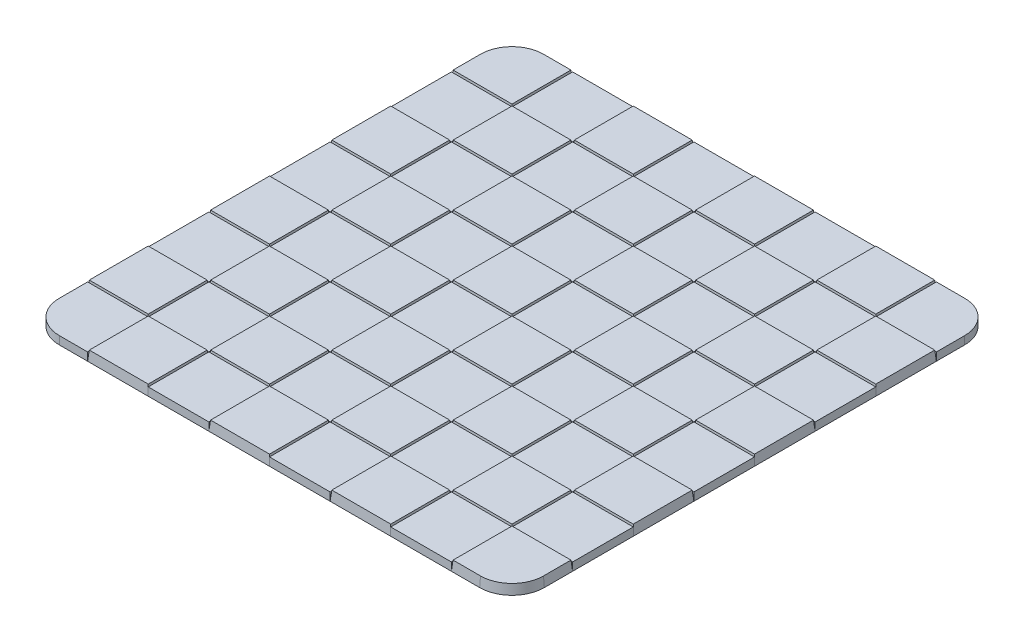
SolidWorks part; units mm, degrees
ref_plane "Front Plane" through (0, 0, 0) normal (0, 0, 1) x (1, 0, 0)
ref_plane "Top Plane" through (0, 0, 0) normal (0, 1, 0) x (1, 0, 0)
ref_plane "Right Plane" through (0, 0, 0) normal (1, 0, 0) x (0, 0, -1)
sketch "Sketch2" plane through (0, 0, 0) normal (0, 1, 0) x (1, 0, 0)
  line L0 (-57.15, 57.15) -> (-38.1, 57.15)
  line L1 (-66.04, 76.2) -> (66.04, 76.2)
  line L2 (-76.2, 66.04) -> (-76.2, -66.04)
  line L3 (-66.04, -76.2) -> (66.04, -76.2)
  line L4 (76.2, 66.04) -> (76.2, -66.04)
  line L5 (-73.2242, 73.2242) -> (73.2242, -73.2242) construction
  line L6 (-73.2242, -73.2242) -> (73.2242, 73.2242) construction
  line L7 (-66.04, 76.2) -> (-57.15, 76.2)
  line L8 (-76.2, 66.04) -> (-76.2, 57.15)
  line L9 (-76.2, 57.15) -> (-57.15, 57.15)
  line L10 (-57.15, 76.2) -> (-57.15, 57.15)
  line L11 (-38.1, 76.2) -> (-38.1, 57.15)
  line L12 (-38.1, 57.15) -> (-19.05, 57.15)
  line L13 (-19.05, 76.2) -> (-19.05, 57.15)
  line L14 (-19.05, 57.15) -> (0, 57.15)
  line L15 (0, 76.2) -> (0, 57.15)
  line L16 (0, 57.15) -> (19.05, 57.15)
  line L17 (19.05, 76.2) -> (19.05, 57.15)
  line L18 (19.05, 57.15) -> (38.1, 57.15)
  line L19 (38.1, 76.2) -> (38.1, 57.15)
  line L20 (38.1, 57.15) -> (57.15, 57.15)
  line L21 (57.15, 76.2) -> (57.15, 57.15)
  line L22 (57.15, 57.15) -> (76.2, 57.15)
  line L23 (76.2, 66.04) -> (76.2, 57.15)
  line L24 (-57.15, 38.1) -> (-38.1, 38.1)
  line L25 (-38.1, 57.15) -> (-38.1, 38.1)
  line L26 (-38.1, 38.1) -> (-19.05, 38.1)
  line L27 (-19.05, 57.15) -> (-19.05, 38.1)
  line L28 (-19.05, 38.1) -> (0, 38.1)
  line L29 (0, 57.15) -> (0, 38.1)
  line L30 (0, 38.1) -> (19.05, 38.1)
  line L31 (19.05, 57.15) -> (19.05, 38.1)
  line L32 (19.05, 38.1) -> (38.1, 38.1)
  line L33 (38.1, 57.15) -> (38.1, 38.1)
  line L34 (38.1, 38.1) -> (57.15, 38.1)
  line L35 (57.15, 57.15) -> (57.15, 38.1)
  line L36 (57.15, 38.1) -> (76.2, 38.1)
  line L37 (76.2, 57.15) -> (76.2, 38.1)
  line L38 (-57.15, 19.05) -> (-38.1, 19.05)
  line L39 (-38.1, 38.1) -> (-38.1, 19.05)
  line L40 (-38.1, 19.05) -> (-19.05, 19.05)
  line L41 (-19.05, 38.1) -> (-19.05, 19.05)
  line L42 (-19.05, 19.05) -> (0, 19.05)
  line L43 (0, 38.1) -> (0, 19.05)
  line L44 (0, 19.05) -> (19.05, 19.05)
  line L45 (19.05, 38.1) -> (19.05, 19.05)
  line L46 (19.05, 19.05) -> (38.1, 19.05)
  line L47 (38.1, 38.1) -> (38.1, 19.05)
  line L48 (38.1, 19.05) -> (57.15, 19.05)
  line L49 (57.15, 38.1) -> (57.15, 19.05)
  line L50 (57.15, 19.05) -> (76.2, 19.05)
  line L51 (76.2, 38.1) -> (76.2, 19.05)
  line L52 (-57.15, 0) -> (-38.1, 0)
  line L53 (-38.1, 19.05) -> (-38.1, 0)
  line L54 (-38.1, 0) -> (-19.05, 0)
  line L55 (-19.05, 19.05) -> (-19.05, 0)
  line L56 (-19.05, 0) -> (0, 0)
  line L57 (0, 19.05) -> (0, 0)
  line L58 (0, 0) -> (19.05, 0)
  line L59 (19.05, 19.05) -> (19.05, 0)
  line L60 (19.05, 0) -> (38.1, 0)
  line L61 (38.1, 19.05) -> (38.1, 0)
  line L62 (38.1, 0) -> (57.15, 0)
  line L63 (57.15, 19.05) -> (57.15, 0)
  line L64 (57.15, 0) -> (76.2, 0)
  line L65 (76.2, 19.05) -> (76.2, 0)
  line L66 (-57.15, -19.05) -> (-38.1, -19.05)
  line L67 (-38.1, 0) -> (-38.1, -19.05)
  line L68 (-38.1, -19.05) -> (-19.05, -19.05)
  line L69 (-19.05, 0) -> (-19.05, -19.05)
  line L70 (-19.05, -19.05) -> (0, -19.05)
  line L71 (0, 0) -> (0, -19.05)
  line L72 (0, -19.05) -> (19.05, -19.05)
  line L73 (19.05, 0) -> (19.05, -19.05)
  line L74 (19.05, -19.05) -> (38.1, -19.05)
  line L75 (38.1, 0) -> (38.1, -19.05)
  line L76 (38.1, -19.05) -> (57.15, -19.05)
  line L77 (57.15, 0) -> (57.15, -19.05)
  line L78 (57.15, -19.05) -> (76.2, -19.05)
  line L79 (76.2, 0) -> (76.2, -19.05)
  line L80 (-57.15, -38.1) -> (-38.1, -38.1)
  line L81 (-38.1, -19.05) -> (-38.1, -38.1)
  line L82 (-38.1, -38.1) -> (-19.05, -38.1)
  line L83 (-19.05, -19.05) -> (-19.05, -38.1)
  line L84 (-19.05, -38.1) -> (0, -38.1)
  line L85 (0, -19.05) -> (0, -38.1)
  line L86 (0, -38.1) -> (19.05, -38.1)
  line L87 (19.05, -19.05) -> (19.05, -38.1)
  line L88 (19.05, -38.1) -> (38.1, -38.1)
  line L89 (38.1, -19.05) -> (38.1, -38.1)
  line L90 (38.1, -38.1) -> (57.15, -38.1)
  line L91 (57.15, -19.05) -> (57.15, -38.1)
  line L92 (57.15, -38.1) -> (76.2, -38.1)
  line L93 (76.2, -19.05) -> (76.2, -38.1)
  line L94 (-57.15, -57.15) -> (-38.1, -57.15)
  line L95 (-38.1, -38.1) -> (-38.1, -57.15)
  line L96 (-38.1, -57.15) -> (-19.05, -57.15)
  line L97 (-19.05, -38.1) -> (-19.05, -57.15)
  line L98 (-19.05, -57.15) -> (0, -57.15)
  line L99 (0, -38.1) -> (0, -57.15)
  line L100 (0, -57.15) -> (19.05, -57.15)
  line L101 (19.05, -38.1) -> (19.05, -57.15)
  line L102 (19.05, -57.15) -> (38.1, -57.15)
  line L103 (38.1, -38.1) -> (38.1, -57.15)
  line L104 (38.1, -57.15) -> (57.15, -57.15)
  line L105 (57.15, -38.1) -> (57.15, -57.15)
  line L106 (57.15, -57.15) -> (76.2, -57.15)
  line L107 (76.2, -38.1) -> (76.2, -57.15)
  line L108 (-57.15, -76.2) -> (-38.1, -76.2)
  line L109 (-38.1, -57.15) -> (-38.1, -76.2)
  line L110 (-38.1, -76.2) -> (-19.05, -76.2)
  line L111 (-19.05, -57.15) -> (-19.05, -76.2)
  line L112 (-19.05, -76.2) -> (0, -76.2)
  line L113 (0, -57.15) -> (0, -76.2)
  line L114 (0, -76.2) -> (19.05, -76.2)
  line L115 (19.05, -57.15) -> (19.05, -76.2)
  line L116 (19.05, -76.2) -> (38.1, -76.2)
  line L117 (38.1, -57.15) -> (38.1, -76.2)
  line L118 (38.1, -76.2) -> (57.15, -76.2)
  line L119 (57.15, -57.15) -> (57.15, -76.2)
  line L120 (57.15, -76.2) -> (66.04, -76.2)
  line L121 (76.2, -57.15) -> (76.2, -66.04)
  line L122 (-76.2, 38.1) -> (-57.15, 38.1)
  line L123 (-57.15, 57.15) -> (-57.15, 38.1)
  line L124 (-76.2, 19.05) -> (-57.15, 19.05)
  line L125 (-57.15, 38.1) -> (-57.15, 19.05)
  line L126 (-76.2, 0) -> (-57.15, 0)
  line L127 (-57.15, 19.05) -> (-57.15, 0)
  line L128 (-76.2, -19.05) -> (-57.15, -19.05)
  line L129 (-57.15, 0) -> (-57.15, -19.05)
  line L130 (-76.2, -38.1) -> (-57.15, -38.1)
  line L131 (-57.15, -19.05) -> (-57.15, -38.1)
  line L132 (-76.2, -57.15) -> (-57.15, -57.15)
  line L133 (-57.15, -38.1) -> (-57.15, -57.15)
  line L134 (-66.04, -76.2) -> (-57.15, -76.2)
  line L135 (-57.15, -57.15) -> (-57.15, -76.2)
  arc A0 (66.04, -76.2) -> (76.2, -66.04) centre (66.04, -66.04) ccw
  arc A1 (-76.2, -66.04) -> (-66.04, -76.2) centre (-66.04, -66.04) ccw
  arc A2 (66.04, 76.2) -> (76.2, 66.04) centre (66.04, 66.04) cw
  arc A3 (-66.04, 76.2) -> (-76.2, 66.04) centre (-66.04, 66.04) ccw
  point P0 (0, 0)
  dimension "D5" = 10.16
  dimension "D2" = 19.05
  dimension "D3" = 8
  dimension "D4" = 8
extrude "Boss-Extrude1" add sketch "Sketch2" along normal blind 2.54 contours L2 A1 L3 L135 L132 | L131 L128 L2 L130 | L127 L124 L2 L126 | L123 L9 L2 L122 | L11 L1 L10 L0 | L15 L1 L13 L14 | L19 L1 L17 L18 | A2 L1 L21 L22 L4 | L49 L50 L4 L36 | L77 L78 L4 L64 | L105 L106 L4 L92 | L119 L104 L117 L3 | L115 L100 L113 L3 | L111 L96 L109 L3 | L80 L133 L94 L95 | L83 L68 L81 L82 | L87 L72 L85 L86 | L91 L76 L89 L90 | L63 L48 L61 L62 | L59 L44 L57 L58 | L55 L40 L53 L54 | L27 L12 L25 L26 | L31 L16 L29 L30 | L35 L20 L33 L34 | L52 L129 L66 L67 | L75 L60 L73 L74 | L47 L32 L45 L46 | L24 L125 L38 L39 | L43 L28 L41 L42 | L71 L56 L69 L70 | L99 L84 L97 L98 | L103 L88 L101 L102 region at (-47.625, 0, -66.675) region at (-66.675, 0, -47.625) region at (-28.575, 0, -47.625) region at (-47.625, 0, -28.575) region at (-9.525, 0, -66.675) region at (-66.675, 0, -9.525) region at (9.525, 0, -47.625) region at (-9.525, 0, -28.575) region at (-28.575, 0, -9.525) region at (-47.625, 0, 9.525) region at (28.575, 0, -66.675) region at (-66.675, 0, 28.575) region at (47.625, 0, -47.625) region at (28.575, 0, -28.575) region at (9.525, 0, -9.525) region at (-9.525, 0, 9.525) region at (-28.575, 0, 28.575) region at (-47.625, 0, 47.625) region at (66.2033, 0, -66.2033) region at (-66.2033, 0, 66.2033) region at (66.675, 0, -28.575) region at (47.625, 0, -9.525) region at (28.575, 0, 9.525) region at (9.525, 0, 28.575) region at (-9.525, 0, 47.625) region at (-28.575, 0, 66.675) region at (66.675, 0, 9.525) region at (47.625, 0, 28.575) region at (28.575, 0, 47.625) region at (9.525, 0, 66.675) region at (66.675, 0, 47.625) region at (47.625, 0, 66.675)
extrude "Boss-Extrude3" add sketch "Sketch2<5>" along normal blind 3.048 draft 5 separate body contours L35 L36 L4 L22 | L21 L1 L19 L20 | L33 L18 L31 L32 | L49 L34 L47 L48 | L63 L64 L4 L50 | L17 L1 L15 L16 | L45 L30 L43 L44 | L13 L1 L11 L12 | L0 L123 L24 L25 | L29 L14 L27 L28 | L41 L26 L39 L40 | L1 A3 L2 L9 L10 | L125 L122 L2 L124 | L129 L126 L2 L128 | L38 L127 L52 L53 | L133 L130 L2 L132 | L66 L131 L80 L81 | L94 L135 L3 L109 | L97 L82 L95 L96 | L69 L54 L67 L68 | L57 L42 L55 L56 | L85 L70 L83 L84 | L73 L58 L71 L72 | L61 L46 L59 L60 | L89 L74 L87 L88 | L77 L62 L75 L76 | L91 L92 L4 L78 | L105 L90 L103 L104 | L3 A0 L4 L106 L119 | L117 L102 L115 L3 | L113 L98 L111 L3 | L101 L86 L99 L100 region at (-66.2033, 0, -66.2033) region at (-47.625, 0, -47.625) region at (-28.575, 0, -66.675) region at (-66.675, 0, -28.575) region at (-9.525, 0, -47.625) region at (-28.575, 0, -28.575) region at (-47.625, 0, -9.525) region at (9.525, 0, -66.675) region at (-66.675, 0, 9.525) region at (28.575, 0, -47.625) region at (9.525, 0, -28.575) region at (-9.525, 0, -9.525) region at (-28.575, 0, 9.525) region at (-47.625, 0, 28.575) region at (47.625, 0, -66.675) region at (-66.675, 0, 47.625) region at (66.675, 0, -47.625) region at (47.625, 0, -28.575) region at (28.575, 0, -9.525) region at (9.525, 0, 9.525) region at (-9.525, 0, 28.575) region at (-28.575, 0, 47.625) region at (-47.625, 0, 66.675) region at (66.675, 0, -9.525) region at (47.625, 0, 9.525) region at (28.575, 0, 28.575) region at (9.525, 0, 47.625) region at (-9.525, 0, 66.675) region at (66.675, 0, 28.575) region at (47.625, 0, 47.625) region at (28.575, 0, 66.675) region at (66.2033, 0, 66.2033)
sketch "Sketch2<5>" plane through (0, 0, 0) normal (0, 1, 0) x (1, 0, 0) same geometry as "Sketch2"
scale "Scale2" bodies to scale 163 162 154 135 112 106 147 126 157 150 138 129 116 160 134 132 111 119 102 141 122 153 105 146 144 125 110 101 156 145 137 149 128 159 115 131 118 109 140 121 scale about origin uniform scaling yes scale factor 2
ref_plane "Plane1" through (0, 5.08, 0) normal (0, 1, 0) x (1, 0, 0)
sketch "Sketch3" plane through (0, 5.08, 0) normal (0, 1, 0) x (1, 0, 0)
  circle A0 centre (-132.08, 132.08) radius 12.065
  circle A1 centre (-94.488, 132.08) radius 12.065
  circle A2 centre (-56.896, 132.08) radius 12.065
  circle A3 centre (-19.304, 132.08) radius 12.065
  circle A4 centre (18.288, 132.08) radius 12.065
  circle A5 centre (55.88, 132.08) radius 12.065
  circle A6 centre (93.472, 132.08) radius 12.065
  circle A7 centre (131.064, 132.08) radius 12.065
  circle A8 centre (-94.488, 94.488) radius 12.065
  circle A9 centre (-56.896, 94.488) radius 12.065
  circle A10 centre (-19.304, 94.488) radius 12.065
  circle A11 centre (18.288, 94.488) radius 12.065
  circle A12 centre (55.88, 94.488) radius 12.065
  circle A13 centre (93.472, 94.488) radius 12.065
  circle A14 centre (131.064, 94.488) radius 12.065
  circle A15 centre (-94.488, 56.896) radius 12.065
  circle A16 centre (-56.896, 56.896) radius 12.065
  circle A17 centre (-19.304, 56.896) radius 12.065
  circle A18 centre (18.288, 56.896) radius 12.065
  circle A19 centre (55.88, 56.896) radius 12.065
  circle A20 centre (93.472, 56.896) radius 12.065
  circle A21 centre (131.064, 56.896) radius 12.065
  circle A22 centre (-94.488, 19.304) radius 12.065
  circle A23 centre (-56.896, 19.304) radius 12.065
  circle A24 centre (-19.304, 19.304) radius 12.065
  circle A25 centre (18.288, 19.304) radius 12.065
  circle A26 centre (55.88, 19.304) radius 12.065
  circle A27 centre (93.472, 19.304) radius 12.065
  circle A28 centre (131.064, 19.304) radius 12.065
  circle A29 centre (-94.488, -18.288) radius 12.065
  circle A30 centre (-56.896, -18.288) radius 12.065
  circle A31 centre (-19.304, -18.288) radius 12.065
  circle A32 centre (18.288, -18.288) radius 12.065
  circle A33 centre (55.88, -18.288) radius 12.065
  circle A34 centre (93.472, -18.288) radius 12.065
  circle A35 centre (131.064, -18.288) radius 12.065
  circle A36 centre (-94.488, -55.88) radius 12.065
  circle A37 centre (-56.896, -55.88) radius 12.065
  circle A38 centre (-19.304, -55.88) radius 12.065
  circle A39 centre (18.288, -55.88) radius 12.065
  circle A40 centre (55.88, -55.88) radius 12.065
  circle A41 centre (93.472, -55.88) radius 12.065
  circle A42 centre (131.064, -55.88) radius 12.065
  circle A43 centre (-94.488, -93.472) radius 12.065
  circle A44 centre (-56.896, -93.472) radius 12.065
  circle A45 centre (-19.304, -93.472) radius 12.065
  circle A46 centre (18.288, -93.472) radius 12.065
  circle A47 centre (55.88, -93.472) radius 12.065
  circle A48 centre (93.472, -93.472) radius 12.065
  circle A49 centre (131.064, -93.472) radius 12.065
  circle A50 centre (-94.488, -131.064) radius 12.065
  circle A51 centre (-56.896, -131.064) radius 12.065
  circle A52 centre (-19.304, -131.064) radius 12.065
  circle A53 centre (18.288, -131.064) radius 12.065
  circle A54 centre (55.88, -131.064) radius 12.065
  circle A55 centre (93.472, -131.064) radius 12.065
  circle A56 centre (131.064, -131.064) radius 12.065
  circle A57 centre (-132.08, 94.488) radius 12.065
  circle A58 centre (-132.08, 56.896) radius 12.065
  circle A59 centre (-132.08, 19.304) radius 12.065
  circle A60 centre (-132.08, -18.288) radius 12.065
  circle A61 centre (-132.08, -55.88) radius 12.065
  circle A62 centre (-132.08, -93.472) radius 12.065
  circle A63 centre (-132.08, -131.064) radius 12.065
  dimension "D1" = 24.13
  dimension "D2" = 8
  dimension "D3" = 8
